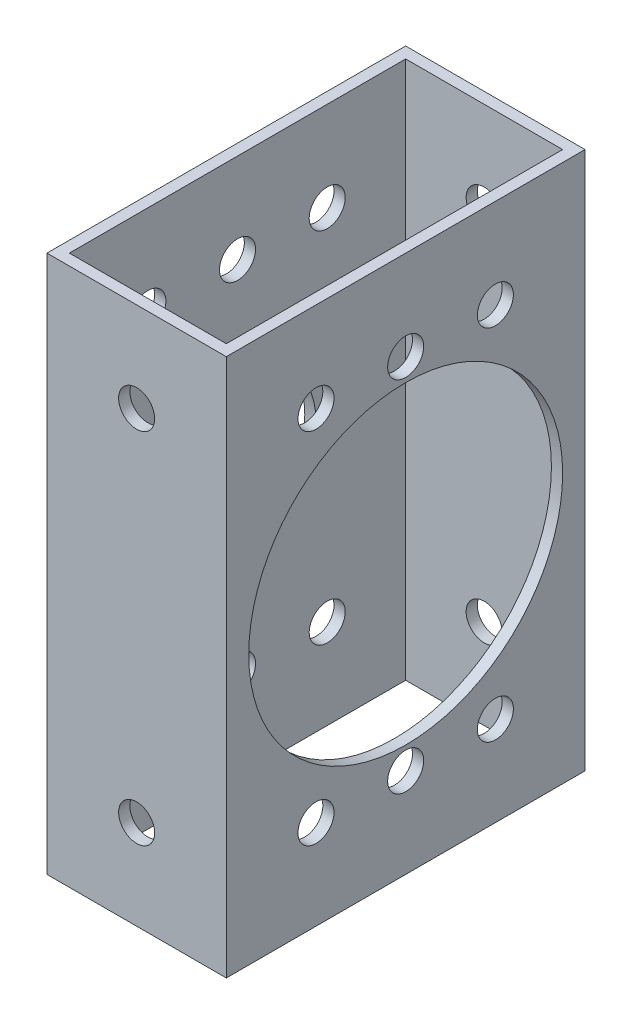
SolidWorks part; units mm, degrees
material "6061-T6 (SS)"
ref_plane "Front" through (0, 0, 0) normal (0, 0, 1) x (1, 0, 0)
ref_plane "Top" through (0, 0, 0) normal (0, 1, 0) x (1, 0, 0)
ref_plane "Right" through (0, 0, 0) normal (1, 0, 0) x (0, 0, -1)
sketch "Sketch1" plane through (0, 0, 0) normal (0, 1, 0) x (1, 0, 0)
  line L1 (12.7, 25.4) -> (-12.7, 25.4)
  line L2 (12.7, 25.4) -> (12.7, -25.4)
  line L3 (12.7, -25.4) -> (-12.7, -25.4)
  line L4 (-12.7, 25.4) -> (-12.7, -25.4)
  line L5 (12.7, 25.4) -> (-12.7, -25.4) construction
  line L6 (12.7, -25.4) -> (-12.7, 25.4) construction
  point P0 (0, 0)
  dimension "D1" = 25.4
  dimension "D2" = 50.8
extrude "Extrude-Thin1" add sketch "Sketch1" along normal up to surface (76.2 mm away) thin thin type one direction reverse wall 1.5875
sketch "Sketch4" plane through (-12.7, 0, 0) normal (-1, 0, 0) x (0, 0, 1)
  line L0 (-12.7, 12.7) -> (12.7, 12.7) construction
  line L3 (-12.7, 63.5) -> (12.7, 63.5) construction
  line L5 (-25.4, 0) -> (25.4, 0) construction
  line L6 (-25.4, 76.2) -> (25.4, 76.2) construction
  point P0 (-12.7, 63.5)
  point P2 (0, 63.5)
  point P4 (12.7, 63.5)
  point P6 (-12.7, 12.7)
  point P8 (0, 12.7)
  point P10 (12.7, 12.7)
  dimension "D1" = 12.7
  dimension "D2" = 12.7
  dimension "D3" = 12.7
  dimension "D4" = 12.7
hole_wizard "#10 Clearance Hole1" positions "Sketch4" profile "Sketch3" hole size "#10" standard "ANSI Inch" end condition through all
sketch "Sketch3" plane through (-12.7, 63.5, -12.7) normal (0, 1, 0) x (0, 0, 1)
  line L0 (0, 0) -> (0, 25.4)
  line L1 (0, 25.4) -> (2.5527, 25.4)
  line L2 (2.5527, 25.4) -> (2.5527, 0)
  line L5 (2.5527, 0) -> (0, 0)
  line L11 (0, -6.35) -> (0, 107.95) construction
  dimension "Thru Hole Dia." = 5.1054
  dimension "Thru Hole Depth" = 25.4
sketch "Sketch7" plane through (0, 0, 25.4) normal (0, 0, 1) x (1, 0, 0)
  line L0 (-12.7, 0) -> (12.7, 0) construction
  line L1 (-12.7, 76.2) -> (12.7, 76.2) construction
  point P0 (0, 12.7)
  point P2 (0, 63.5)
  dimension "D1" = 12.7
  dimension "D2" = 12.7
hole_wizard "#10 Clearance Hole2" positions "Sketch7" profile "Sketch6" hole size "#10" standard "ANSI Inch" end condition through all
sketch "Sketch6" plane through (0, 12.7, 25.4) normal (1, 0, 0) x (0, -1, 0)
  line L0 (0, 0) -> (0, 50.8)
  line L1 (0, 50.8) -> (2.5527, 50.8)
  line L2 (2.5527, 50.8) -> (2.5527, 0)
  line L5 (2.5527, 0) -> (0, 0)
  line L11 (0, -6.35) -> (0, 107.95) construction
  dimension "Thru Hole Dia." = 5.1054
  dimension "Thru Hole Depth" = 50.8
sketch "Sketch8" plane through (-12.7, 0, 0) normal (-1, 0, 0) x (0, 0, 1)
  line L0 (-25.4, 0) -> (25.4, 76.2) construction
  line L1 (25.4, 76.2) -> (25.4, 0) construction
  line L2 (-25.4, 76.2) -> (25.4, 76.2) construction
  line L3 (-25.4, 76.2) -> (-25.4, 0) construction
  line L4 (-25.4, 0) -> (25.4, 0) construction
  line L5 (10.8183, 40.64) -> (13.0175, 40.64)
  line L7 (13.0175, 35.56) -> (10.8183, 35.56)
  arc A0 (10.8183, 40.64) -> (10.8183, 35.56) centre (0, 38.1) ccw
  arc A1 (13.0175, 40.64) -> (13.0175, 35.56) centre (13.0175, 38.1) cw
  dimension "D1" = 22.225
  dimension "D2" = 4.445
  dimension "D3" = 5.08
extrude "Cut-Extrude1" cut sketch "Sketch8" against normal through all
sketch "Sketch9" plane through (12.7, 0, 0) normal (1, 0, 0) x (0, 0, -1)
  circle A0 centre (0, 38.1) radius 22.225
  circle A1 centre (0, 38.1) radius 11.1125 construction
  dimension "D1" = 44.45
extrude "Cut-Extrude2" cut sketch "Sketch9" against normal up to next
